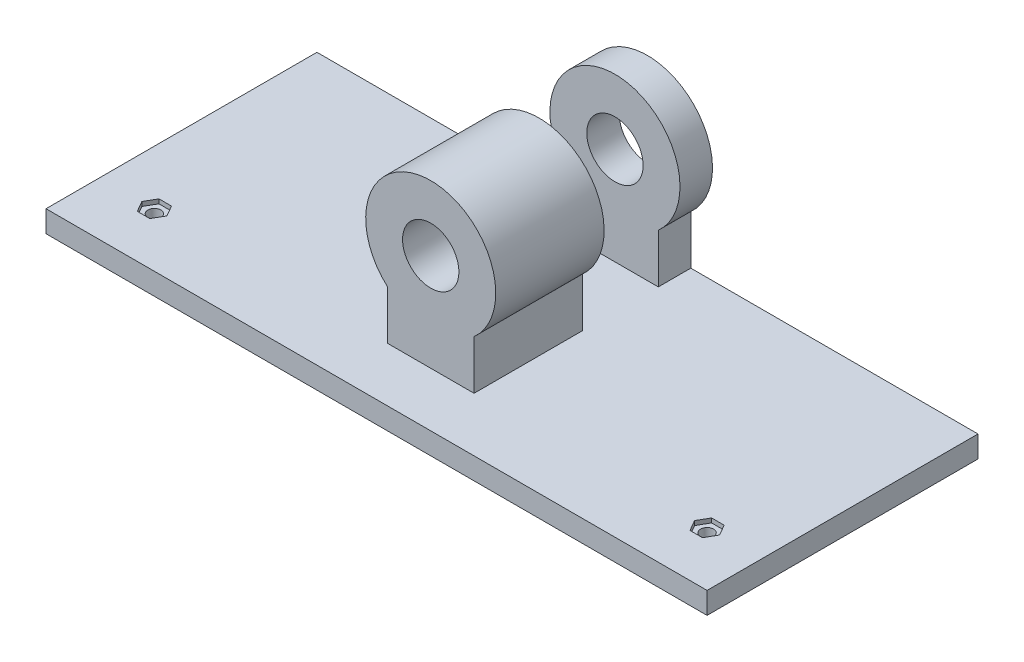
SolidWorks part; units mm, degrees
ref_plane "Front Plane" through (0, 0, 0) normal (0, 0, 1) x (1, 0, 0)
ref_plane "Top Plane" through (0, 0, 0) normal (0, 1, 0) x (1, 0, 0)
ref_plane "Right Plane" through (0, 0, 0) normal (1, 0, 0) x (0, 0, -1)
sketch "Sketch1" plane through (0, 0, 0) normal (0, 1, 0) x (1, 0, 0)
  line L0 (152.5, 125) -> (152.5, 0) construction
  line L1 (0, 0) -> (305, 0)
  line L2 (0, 0) -> (0, 125)
  line L3 (0, 125) -> (305, 125)
  line L4 (305, 0) -> (305, 125)
  line L5 (25, 100) -> (280, 100) construction
  line L6 (280, 25) -> (280, 100) construction
  line L7 (25, 25) -> (280, 25) construction
  line L8 (25, 25) -> (25, 100) construction
  line L9 (152.5, 62.5) -> (25, 62.5) construction
  line L10 (30.7735, 100) -> (27.8868, 105) construction
  line L11 (27.8868, 105) -> (22.1132, 105) construction
  line L12 (22.1132, 105) -> (19.2265, 100) construction
  line L13 (19.2265, 100) -> (22.1132, 95) construction
  line L14 (22.1132, 95) -> (27.8868, 95) construction
  line L15 (27.8868, 95) -> (30.7735, 100) construction
  line L16 (27.8868, 30) -> (30.7735, 25) construction
  line L17 (22.1132, 30) -> (27.8868, 30) construction
  line L18 (19.2265, 25) -> (22.1132, 30) construction
  line L19 (22.1132, 20) -> (19.2265, 25) construction
  line L20 (27.8868, 20) -> (22.1132, 20) construction
  line L21 (30.7735, 25) -> (27.8868, 20) construction
  line L22 (282.8868, 30) -> (277.1132, 30) construction
  line L23 (285.7735, 25) -> (282.8868, 30) construction
  line L24 (282.8868, 20) -> (285.7735, 25) construction
  line L25 (277.1132, 20) -> (282.8868, 20) construction
  line L26 (274.2265, 25) -> (277.1132, 20) construction
  line L27 (277.1132, 30) -> (274.2265, 25) construction
  line L28 (277.1132, 95) -> (274.2265, 100) construction
  line L29 (282.8868, 95) -> (277.1132, 95) construction
  line L30 (285.7735, 100) -> (282.8868, 95) construction
  line L31 (282.8868, 105) -> (285.7735, 100) construction
  line L32 (277.1132, 105) -> (282.8868, 105) construction
  line L33 (274.2265, 100) -> (277.1132, 105) construction
  circle A1 centre (25, 100) radius 5 construction
  circle A3 centre (280, 25) radius 3
  circle A4 centre (25, 25) radius 3
  dimension "D3" = 6
  dimension "D1" = 305
  dimension "D2" = 125
  dimension "D5" = 10
  dimension "D4" = 25
extrude "Boss-Extrude1" add sketch "Sketch1" along normal blind 10
sketch "Sketch6" plane through (0, 10, 0) normal (0, 1, 0) x (1, 0, 0)
  line L0 (152.5, 125) -> (152.5, 0) construction
  line L7 (305, 125) -> (0, 125) construction
  line L8 (0, 0) -> (305, 0) construction
  line L9 (152.5, 62.5) -> (0, 62.5) construction
  line L10 (0, 125) -> (0, 0) construction
  line L29 (27.8868, 30) -> (30.7735, 25)
  line L30 (274.2265, 25) -> (277.1132, 20)
  line L31 (277.1132, 20) -> (282.8868, 20)
  line L32 (282.8868, 20) -> (285.7735, 25)
  line L33 (285.7735, 25) -> (282.8868, 30)
  line L34 (282.8868, 30) -> (277.1132, 30)
  line L35 (277.1132, 30) -> (274.2265, 25)
  line L36 (22.1132, 30) -> (27.8868, 30)
  line L37 (19.2265, 25) -> (22.1132, 30)
  line L38 (22.1132, 20) -> (19.2265, 25)
  line L39 (27.8868, 20) -> (22.1132, 20)
  line L40 (30.7735, 25) -> (27.8868, 20)
  circle A0 centre (280, 25) radius 5 construction
  dimension "D1" = 10
extrude "Cut-Extrude1" cut sketch "Sketch6" against normal blind 2
sketch "Sketch7" plane through (0, 10, 0) normal (0, 1, 0) x (1, 0, 0)
  line L0 (0, 0) -> (305, 0) construction
  line L1 (132.5, 25) -> (172.5, 25)
  line L2 (132.5, 25) -> (132.5, 75)
  line L3 (132.5, 75) -> (172.5, 75)
  line L4 (172.5, 25) -> (172.5, 75)
  line L5 (152.5, 0) -> (152.5, 125) construction
  line L6 (305, 125) -> (0, 125) construction
  line L7 (172.5, 75) -> (172.5, 125) construction
  line L18 (132.5, 110) -> (172.5, 110)
  line L19 (132.5, 110) -> (132.5, 125)
  line L20 (132.5, 125) -> (172.5, 125)
  line L21 (172.5, 110) -> (172.5, 125)
  point P11 (152.5, 75)
  point P20 (152.5, 110)
  dimension "D1" = 40
  dimension "D4" = 15
extrude "Boss-Extrude2" add sketch "Sketch7" along normal blind 22.6393
sketch "Sketch11" plane through (0, 0, -25) normal (0, 0, 1) x (1, 0, 0)
  circle A0 centre (152.5, 55) radius 30
  circle A1 centre (152.5, 55) radius 13
  dimension "D1" = 60
  dimension "D2" = 26
extrude "Boss-Extrude3" add sketch "Sketch11" against normal up to surface (100 mm away) up to face at (152.5, 13.1598, -125)
ref_plane "Plane1" through (0, 0, -62.5) normal (0, 0, 1) x (1, 0, 0)
sketch "Sketch12" plane through (305, 0, 0) normal (1, 0, 0) x (0, 0, -1)
  line L0 (125, 85) -> (25, 85) construction
  line L1 (75, 10) -> (110, 10)
  line L2 (75, 10) -> (75, 85)
  line L3 (75, 85) -> (110, 85)
  line L4 (110, 10) -> (110, 85)
  line L6 (110, 32.6393) -> (110, 10) construction
extrude "Cut-Extrude2" cut sketch "Sketch12" against normal through all
equation "\"joint_width\"=4"
equation "\"D2@Sketch7\"=5"
equation "\"short_base_length\"=12.5"
equation "\"D2@Sketch1\"=\"short_base_length\""
equation "\"outer_diam_main_joint\"=6"
equation "\"D1@Sketch11\"=\"outer_diam_main_joint\""
equation "\"D1@Sketch7\"=\"outer_diam_main_joint\"-2"
equation "\"D1@Boss-Extrude2\"=(\"outer_diam_main_joint\"/2)+1.5cm-sqr((\"outer_diam_main_joint\"/2)^2-((\"outer_diam_main_joint\"-2)/2)^2)"
